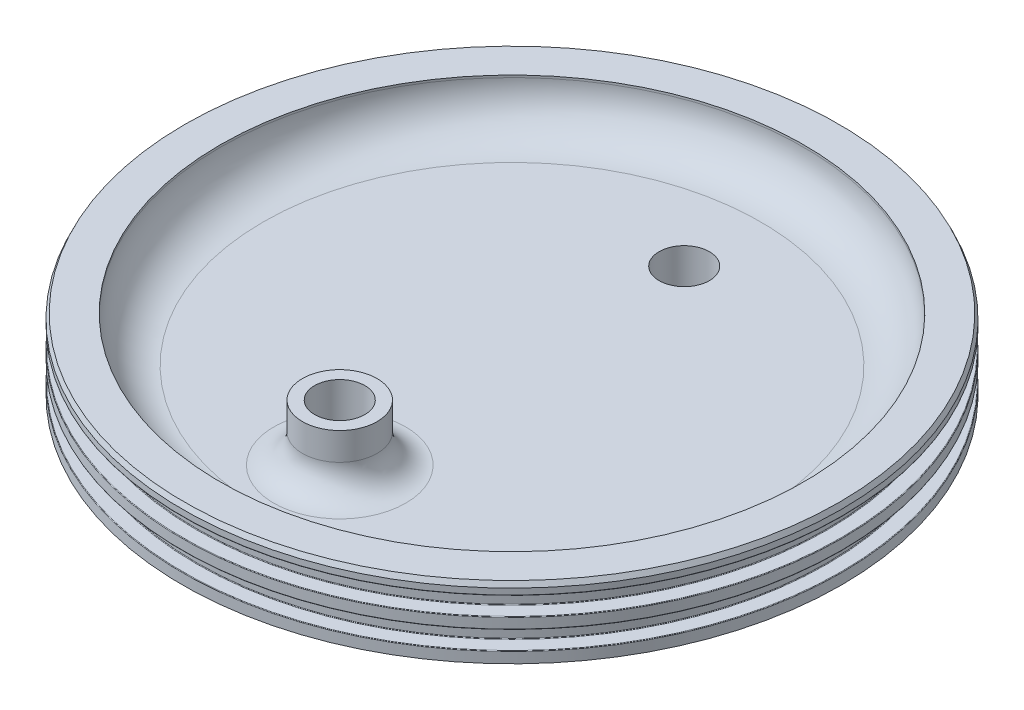
SolidWorks part; units mm, degrees
material "6061-T6 (SS)"
ref_plane "Front Plane" through (0, 0, 0) normal (0, 0, 1) x (1, 0, 0)
ref_plane "Top Plane" through (0, 0, 0) normal (0, 1, 0) x (1, 0, 0)
ref_plane "Right Plane" through (0, 0, 0) normal (1, 0, 0) x (0, 0, -1)
sketch "Sketch1" plane through (0, 0, 0) normal (0, 0, 1) x (1, 0, 0)
  line L0 (0, 48.1922) -> (0, -25.6743) construction
  line L1 (0, 0) -> (72.898, 0)
  line L2 (72.898, 0) -> (72.898, 2.4638)
  line L3 (72.898, 2.4638) -> (69.6468, 2.4638)
  line L4 (69.6468, 2.4638) -> (69.6468, 6.5278)
  line L5 (69.6468, 6.5278) -> (72.898, 6.5278)
  line L6 (72.898, 6.5278) -> (72.898, 8.9916)
  line L7 (72.898, 8.9916) -> (69.6468, 8.9916)
  line L8 (64.5668, 15.5956) -> (64.5668, 5.588)
  line L9 (64.5668, 5.588) -> (0, 5.588)
  line L10 (0, 5.588) -> (0, 0)
  line L11 (69.6468, 8.9916) -> (69.6468, 13.0556)
  line L12 (69.6468, 13.0556) -> (72.898, 13.0556)
  line L13 (72.898, 13.0556) -> (72.898, 15.5956)
  line L14 (72.898, 15.5956) -> (64.5668, 15.5956)
  dimension "D1" = 145.796
  dimension "D2" = 4.064
  dimension "D5" = 5.588
  dimension "D7" = 4.064
  dimension "D4" = 2.4638
  dimension "D8" = 2.54
  dimension "D3" = 69.6468
  dimension "D6" = 5.08
revolve "Revolve1" add sketch "Sketch1" angle 360 about L0
sketch "Sketch6" plane through (0, 0, 0) normal (0, -1, 0) x (1, 0, 0)
  circle A0 centre (0, 0) radius 66.04
  dimension "D1" = 132.08
extrude "Boss-Extrude1" add sketch "Sketch6" along normal blind 2.54
hole_wizard "Pipe Tap Drill for 1/4 Tap - GN2" positions "Sketch2" profile "Sketch3" hole size "1/4" standard "ANSI Inch" end condition through all
sketch "Sketch2" plane through (0, 5.588, 0) normal (0, 1, 0) x (1, 0, 0)
  point P4 (0, -38.1)
  dimension "D1" = 38.1
sketch "Sketch3" plane through (0, 5.588, 38.1) normal (1, 0, 0) x (0, 0, 1)
  line L0 (0, 0) -> (0, 8.128)
  line L1 (0, 8.128) -> (5.5626, 8.128)
  line L2 (5.5626, 8.128) -> (5.5626, 0)
  line L5 (5.5626, 0) -> (0, 0)
  line L11 (0, -6.35) -> (0, 107.95) construction
  dimension "Thru Hole Dia." = 11.1252
  dimension "Thru Hole Depth" = 8.128
fillet "CNC ID Fillet" radius 0.127 5 edges at (-69.6468, 6.5278, 0) (-69.6468, 2.4638, 0) (-69.6468, 13.0556, 0) (-69.6468, 8.9916, 0) (66.04, 0, 0)
fillet "CNC OD Fillet" radius 0.127 5 edges at (-72.898, 6.5278, 0) (-72.898, 2.4638, 0) (66.04, -2.54, 0) (-72.898, 13.0556, 0) (-72.898, 8.9916, 0)
chamfer "CNC Chamfers" distance 0.508 angle 65 1 edges at (-72.898, 15.5956, 0) first distance on face at (-64.5668, 15.5956, 0)
hole_wizard "Pipe Tap Drill for 1/4 Tap - Relief Valve" positions "Sketch13" profile "Sketch14" hole size "1/4" standard "ANSI Inch" end condition through all
sketch "Sketch13" plane through (0, -2.54, 0) normal (0, -1, 0) x (-1, 0, 0)
  point P4 (0, 38.1)
  dimension "D1" = 38.1
sketch "Sketch14" plane through (0, -2.54, -38.1) normal (1, 0, 0) x (0, 0, -1)
  line L0 (0, 0) -> (0, 18.1356)
  line L1 (0, 18.1356) -> (5.5626, 18.1356)
  line L2 (5.5626, 18.1356) -> (5.5626, 0)
  line L5 (5.5626, 0) -> (0, 0)
  line L11 (0, -6.35) -> (0, 107.95) construction
  dimension "Thru Hole Dia." = 11.1252
  dimension "Thru Hole Depth" = 18.1356
sketch "Sketch15" plane through (0, -2.54, 0) normal (0, -1, 0) x (1, 0, 0)
  circle A0 centre (0, 38.1) radius 8.255
  circle A1 centre (0, 38.1) radius 5.5626 construction
  circle A2 centre (0, 38.1) radius 5.5626
  dimension "D1" = 16.51
extrude "Boss-Extrude2" add sketch "Sketch15" against normal blind 12.446 from surface starting at face at (5.5626, 5.588, -38.1)
fillet "Fillet2" radius 6.35 1 edges at (8.255, 5.588, 38.1)
fillet "Fillet3" radius 9.525 1 edges at (-64.5668, 5.588, 0)
sketch "Sketch16" plane through (0, -2.54, 0) normal (0, -1, 0) x (1, 0, 0)
  line L0 (0, 38.1) -> (0, -38.1) construction
  line L1 (25.4, 30.48) -> (-25.4, 30.48) construction
  line L2 (-9.4223, 0) -> (9.4223, 0) construction
  line L3 (25.4, -30.48) -> (-25.4, -30.48) construction
  text T0 "GN2"
  text T1 "VENT\r\n"
  point P7 (0, 30.48)
  point P14 (0, 0)
  dimension "D1" = 50.8
  dimension "D2" = 7.62
equation "\"D3@Sketch1\"=5.484/2"
